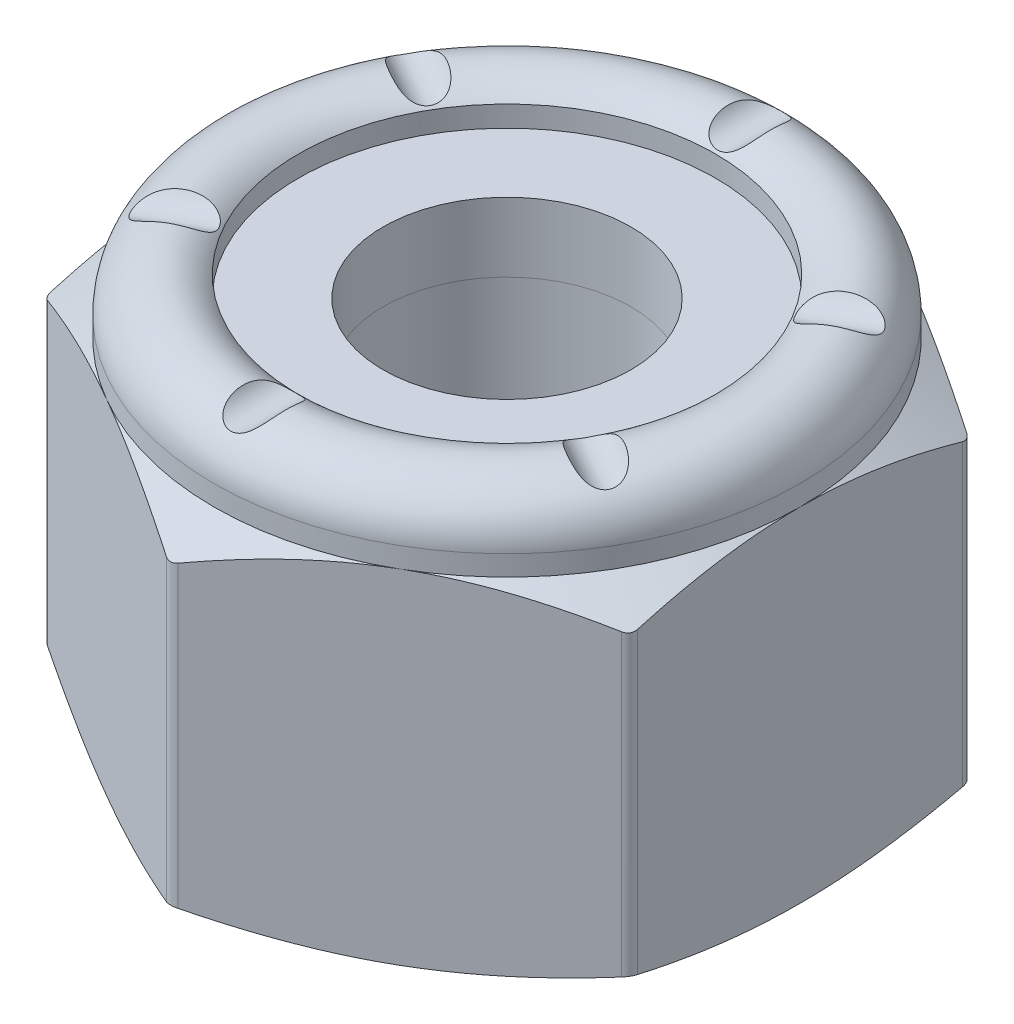
SolidWorks part; units mm, degrees
ref_plane "Front Plane" through (0, 0, 0) normal (0, 0, 1) x (1, 0, 0)
ref_plane "Top Plane" through (0, 0, 0) normal (0, 1, 0) x (1, 0, 0)
ref_plane "Right Plane" through (0, 0, 0) normal (1, 0, 0) x (0, 0, -1)
sketch "Sketch1" plane through (0, 0, 0) normal (0, 0, 1) x (1, 0, 0)
  line L0 (0, -3.9688) -> (0, 3.9688) construction
  line L1 (5.5562, 0) -> (-5.5562, 0) construction
  line L2 (3.175, -3.9688) -> (-3.175, -3.9688) construction
  line L3 (3.175, -3.9688) -> (3.175, -2.6987) construction
  point P4 (0, 0)
  point P8 (0, 0)
  point P11 (0, -3.9688)
  dimension "Height" = 7.9375
  dimension "Width" = 11.1125
  dimension "Thread Size" = 6.35
  dimension "Thread Pitch" = 1.27
sketch "Sketch2" plane through (0, 0, 0) normal (0, 1, 0) x (1, 0, 0)
  line L0 (-3.175, 0.5556) -> (-3.175, -0.5556) construction
  line L1 (0, 6.4158) -> (-5.5562, 3.2079)
  line L2 (-5.5562, 3.2079) -> (-5.5562, -3.2079)
  line L3 (-5.5562, -3.2079) -> (0, -6.4158)
  line L4 (0, -6.4158) -> (5.5563, -3.2079)
  line L5 (5.5563, -3.2079) -> (5.5563, 3.2079)
  line L6 (5.5563, 3.2079) -> (0, 6.4158)
  line L7 (-3.175, -0.5556) -> (-2.3501, -0.0794) construction
  line L8 (-2.3501, -0.0794) -> (-2.3501, 0.0794) construction
  line L9 (-2.3501, 0.0794) -> (-3.175, 0.5556) construction
  line L10 (-2.3501, 0) -> (-3.175, 0) construction
  line L11 (-2.7626, 0.3175) -> (-2.7626, -0.3175) construction
  line L12 (3.175, 0) -> (-3.175, 0) construction
  line L13 (5.5562, 0) -> (-5.5562, 0) construction
  circle A0 centre (0, 0) radius 5.5563 construction
  circle A1 centre (0, 0) radius 2.3501
  point P19 (0, -2.3501)
  dimension "D1" = 0.1588
  dimension "D2" = 0.635
  dimension "D3" = 60
extrude "Boss-Extrude1" add sketch "Sketch2" along normal up to vertex (3.9688 mm away) and the other way up to vertex (3.9688 mm away) up to point (0, 3.9688, 0) other way up to point (0, -3.9688, 0)
fillet "Fillet1" radius 0.2223 6 edges at (-5.5562, 0, -3.2079) (0, 0, -6.4158) (-5.5562, 0, 3.2079) (5.5563, 0, -3.2079) (5.5563, 0, 3.2079) (0, 0, 6.4158)
sketch "Sketch3" plane through (0, 0, 0) normal (1, 0, 0) x (0, 0, -1)
  line L0 (6.4158, 2.6458) -> (6.4158, 4.9688)
  line L1 (3.9532, 1.9844) -> (5.5563, 1.9844) construction
  line L2 (5.334, -3.9688) -> (6.4158, -3.4643)
  line L3 (3.2721, -3.9688) -> (6.3516, -3.9688) construction
  line L4 (6.4158, 3.9688) -> (6.4158, -3.9688) construction
  line L5 (6.4158, -3.4643) -> (6.4158, -3.9688)
  line L6 (6.4158, -3.9688) -> (5.334, -3.9688)
  line L7 (5.5563, 2.6458) -> (6.4158, 2.1414)
  line L8 (6.4158, 2.1414) -> (6.4158, 2.6458)
  line L9 (5.5563, 1.9844) -> (5.5563, 2.6458) construction
  line L10 (3.2721, -3.9688) -> (6.3516, -3.9688) construction
  line L11 (5.5563, 2.6458) -> (5.5563, 3.0297)
  line L12 (3.2721, 3.9688) -> (6.3516, 3.9688) construction
  line L13 (2.3501, 1.9844) -> (3.9532, 1.9844)
  line L14 (3.9532, 1.9844) -> (3.9532, 3.6937)
  line L16 (3.9532, 3.6937) -> (4.6172, 3.0297) construction
  line L17 (4.6172, 3.0297) -> (4.6172, 3.9688) construction
  line L18 (2.3501, 1.9844) -> (2.3501, 4.9688)
  line L19 (2.3501, 4.9688) -> (6.4158, 4.9688)
  line L21 (2.3501, -3.9688) -> (2.3501, -3.3338)
  line L22 (-3.0796, -3.9688) -> (3.0796, -3.9688) construction
  line L24 (2.9851, -3.9688) -> (2.3501, -3.9688)
  line L25 (2.3501, -3.3338) -> (2.9851, -3.9688)
  arc A0 (5.5563, 3.0297) -> (3.9532, 3.6937) centre (4.6172, 3.0297) ccw
  point P0 (5.5563, 2.6458)
  point P1 (5.5563, 0)
  point P14 (2.3501, 0)
  point P36 (5.5563, -3.9688)
  dimension "D1" = 6.6146
  dimension "D2" = 25
  dimension "D3" = 45
  dimension "D4" = 1
  dimension "D5" = 0.635
  dimension "D6" = 5.9531
  dimension "D7" = 0.2223
revolve "Cut-Revolve2" cut sketch "Sketch3" angle 360 about L0
sketch "Sketch4" plane through (0, 0, 0) normal (1, 0, 0) x (0, 0, -1)
  line L0 (-3.9532, 3.6937) -> (-3.9532, 1.9844) construction
  line L1 (-2.3501, 1.9844) -> (-3.9532, 1.9844)
  line L2 (-2.3501, 1.9844) -> (-2.3501, 3.2968)
  line L3 (-2.3501, 3.2968) -> (-3.9532, 3.2968)
  line L4 (-3.9532, 1.9844) -> (-3.9532, 3.2968)
  line L5 (3.9532, 3.6937) -> (-3.9532, 3.6937) construction
  line L6 (2.3501, 1.9844) -> (-2.3501, 1.9844) construction
  dimension "D1" = 0.3969
sketch "Sketch11" plane through (0, 0, 0) normal (1, 0, 0) x (0, 0, -1)
  line L0 (4.6172, 3.0297) -> (4.6172, 3.2645) construction
  line L1 (4.6172, 3.0297) -> (4.6172, 3.9688) construction
  line L2 (4.6172, 3.2645) -> (4.6172, 3.4992) construction
  line L3 (4.6172, 3.4992) -> (4.6172, 3.734) construction
  line L4 (4.6172, 3.734) -> (4.6172, 3.9688) construction
  line L5 (3.9532, 1.9844) -> (3.9532, 3.6937) construction
  line L7 (3.9532, 4.2035) -> (3.9532, 3.734)
  line L8 (3.9532, 3.734) -> (5.5563, 3.734)
  line L9 (5.5563, 4.2035) -> (5.5563, 3.734)
  line L10 (5.5563, 1.9844) -> (5.5563, 2.6458) construction
  line L11 (3.9532, 3.9688) -> (5.5563, 3.9688) construction
  line L12 (3.9532, 4.2035) -> (5.5563, 4.2035)
revolve "Cut-Revolve5" cut sketch "Sketch11" angle 360 about L12
pattern_circular "CirPattern1" count 6 over 360 about axis through (0, -3.9688, 0) along (0, 1, 0) of "Cut-Revolve5" reverse direction yes
revolve "Revolve1" add sketch "Sketch4" angle 360 about L0
sketch "Sketch5" plane through (0, 0, 0) normal (0, 1, 0) x (1, 0, 0)
  circle A0 centre (0, 0) radius 2.3501 construction
  point P0 (0, -2.3501)
sketch "Sketch6" [suppressed] plane through (0, 0, 0) normal (0, 0, 1) x (1, 0, 0)
  line L0 (3.175, 2.6458) -> (3.175, -3.9688)
  line L2 (0, -3.9688) -> (5.5563, -3.9688) construction
  line L3 (3.175, -3.9688) -> (0, -3.9688)
  line L4 (0, -3.9688) -> (0, 2.6458)
  line L5 (0, -3.9688) -> (0, 3.9688) construction
  line L6 (0, 2.6458) -> (3.175, 2.6458)
  line L7 (5.5563, 2.6458) -> (2.7781, 2.6458) construction
revolve "Revolve2" [suppressed] add sketch "Sketch6" angle 360 about L4
sketch "Sketch7" [suppressed] plane through (0, -3.9688, 0) normal (0, -1, 0) x (1, 0, 0)
  circle A2 centre (0, 0) radius 3.175
  circle A3 centre (0, 0) radius 3.175
  dimension "D1" = 0
curve "Helix/Spiral1" [suppressed] pitch 1.27 height 7.9375 turns 6.25
sketch "Sketch8" [suppressed] plane through (0, 0, 0) normal (0, 0, 1) x (1, 0, 0)
  line L0 (3.3125, -3.8894) -> (2.2126, -4.5244) construction
  line L1 (2.2126, -4.5244) -> (3.3125, -5.1594) construction
  line L2 (3.3125, -5.1594) -> (3.3125, -3.8894) construction
  line L3 (2.3501, -4.445) -> (2.3501, -4.6038)
  line L4 (3.175, -3.9688) -> (3.175, -5.08) construction
  line L5 (3.175, -4.5244) -> (3.3125, -4.5244) construction
  line L6 (2.2126, -4.5244) -> (2.3501, -4.5244) construction
  line L7 (3.2437, -4.5244) -> (3.2437, -5.1197) construction
  line L8 (2.3501, -4.445) -> (3.3125, -3.8894)
  line L9 (3.3125, -3.8894) -> (3.2437, -5.1197)
  line L10 (2.3501, -4.6038) -> (3.2437, -5.1197)
  dimension "D1" = 1.27
  dimension "D2" = 0.1588
sweep "Cut-Sweep1" [suppressed] cut profiles "Sketch8" path "Helix/Spiral1"
sketch "Sketch9" [suppressed] plane through (0, 0, 0) normal (0, 0, 1) x (1, 0, 0)
  line L0 (0, -0.7938) -> (0, -3.9688)
  line L1 (0, -0.7938) -> (0, -0.1588)
  line L2 (0, -3.9688) -> (3.175, -3.9688)
  line L3 (3.175, -3.9688) -> (3.81, -3.9688)
  line L4 (3.81, -3.9688) -> (0, -0.1588)
  dimension "D1" = 0.635
revolve "Revolve3" [suppressed] add sketch "Sketch9" angle 360 about L0
sketch "Sketch10" [suppressed] plane through (0, -3.9688, 0) normal (0, -1, 0) x (1, 0, 0)
  circle A0 centre (0, 0) radius 2.9851 construction
  circle A1 centre (0, 0) radius 2.9851
extrude "Boss-Extrude2" [suppressed] add sketch "Sketch10" against normal up to surface (5.9531 mm away)
combine bodies "Combine1" [suppressed] operation type subtract main body 110 bodies to subtract 109
equation "\"D1@Sketch3\"=\"Height@Sketch1\" *  ( 5/6)"
equation "\"D5@Sketch3\"=\"Thread Size@Sketch1\"*.1"
equation "\"D4@Helix/Spiral1\"=\"Thread Pitch@sketch1\""
equation "\"D3@Helix/Spiral1\"=\"Height@sketch1\""
equation "\"D1@Sketch8\"=\"Thread Pitch@sketch1\""
equation "\"D2@Sketch8\"=\"Thread Pitch@sketch1\"/8"
equation "\"D1@Sketch9\"=\"Thread Size@Sketch1\" * .1"
equation "\"D1@Sketch2\"=\"Thread Pitch@sketch1\"/8"
equation "\"D2@Sketch2\"=\"Thread Pitch@sketch1\"/2"
equation "\"D1@Sketch4\"=\"Height@Sketch1\" * .05"
equation "\"D1@Fillet1\"=\"Width@sketch1\"*.02"
equation "\"D6@Sketch3\"=\"Height@Sketch1\" *.75"
equation "\"D7@Sketch3\"=\"Width@Sketch1\"*.02"
